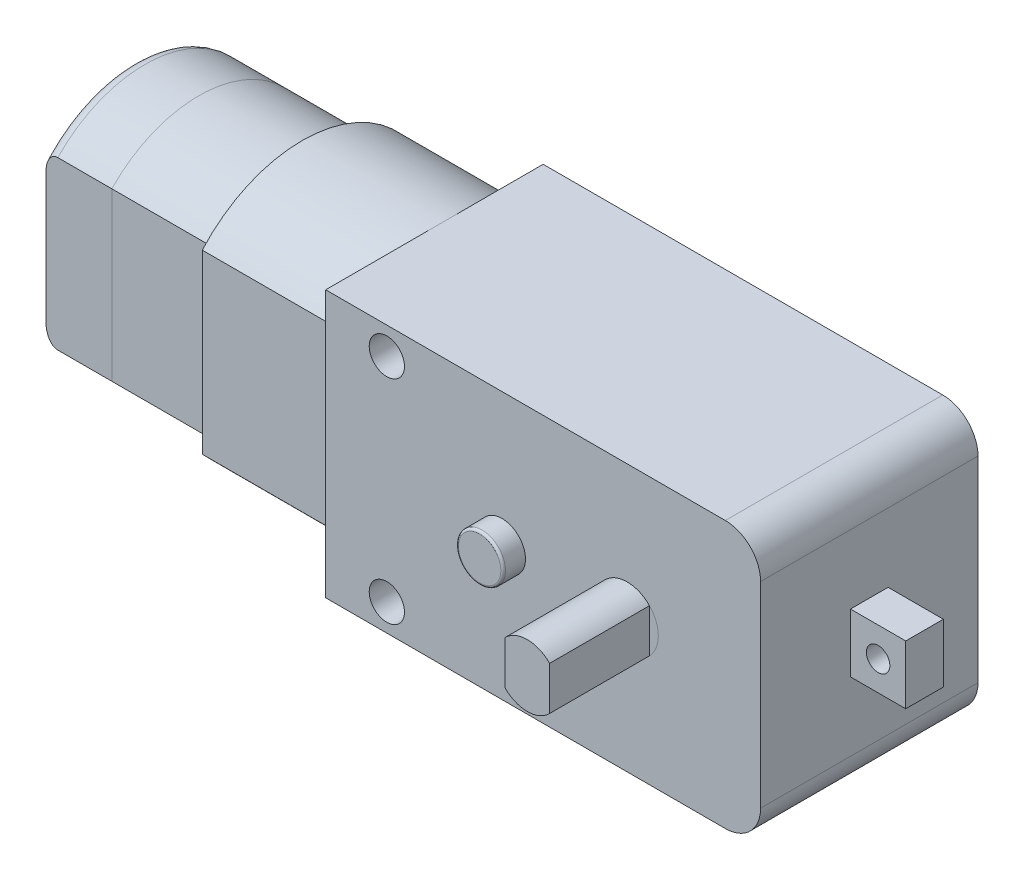
SolidWorks part; units mm, degrees
ref_plane "Alzado" through (0, 0, 0) normal (0, 0, 1) x (1, 0, 0)
ref_plane "Planta" through (0, 0, 0) normal (0, 1, 0) x (1, 0, 0)
ref_plane "Vista lateral" through (0, 0, 0) normal (1, 0, 0) x (0, 0, -1)
sketch "Croquis1" plane through (0, 0, 0) normal (0, 0, 1) x (1, 0, 0)
  line L1 (-18.5, -11.35) -> (15.5, -11.35)
  line L2 (-18.5, -11.35) -> (-18.5, 11.35)
  line L3 (-18.5, 11.35) -> (15.5, 11.35)
  line L4 (18.5, -8.35) -> (18.5, 8.35)
  line L5 (-18.5, -11.35) -> (18.5, 11.35) construction
  line L6 (-18.5, 11.35) -> (18.5, -11.35) construction
  arc A0 (15.5, -11.35) -> (18.5, -8.35) centre (15.5, -8.35) ccw
  arc A1 (15.5, 11.35) -> (18.5, 8.35) centre (15.5, 8.35) cw
  point P0 (0, 0)
  dimension "D3" = 3
  dimension "D1" = 22.7
  dimension "D2" = 37
extrude "Saliente-Extruir1" add sketch "Croquis1" along normal blind 9.25 and the other way blind 9.25
sketch "Croquis2" plane through (-18.5, 0, 0) normal (-1, 0, 0) x (0, 0, 1)
  line L0 (-0.75, -11.35) -> (-0.75, 11.35) construction
  line L1 (7.75, -7.5215) -> (7.75, 7.5215)
  line L2 (-9.25, -7.5215) -> (-9.25, 7.5215)
  line L3 (9.25, 11.35) -> (9.25, -11.35) construction
  line L5 (7.75, -12.1318) -> (7.75, 11.35) construction
  line L6 (-9.25, -12.1318) -> (-9.25, 11.35) construction
  line L7 (-0.75, -12.1318) -> (-0.75, 11.35) construction
  arc A0 (7.75, 7.5215) -> (-9.25, 7.5215) centre (-0.75, 0) ccw
  arc A1 (-9.25, -7.5215) -> (7.75, -7.5215) centre (-0.75, 0) ccw
  point P8 (-0.75, 0)
  dimension "D1" = 22.7
  dimension "D2" = 8.5
  dimension "D3" = 8.5
  dimension "D4" = 1.5
extrude "Saliente-Extruir2" add sketch "Croquis2" along normal blind 12
sketch "Croquis3" plane through (18.5, 0, 0) normal (1, 0, 0) x (0, 0, -1)
  line L1 (1.6, -2.5) -> (-1.6, -2.5)
  line L2 (1.6, -2.5) -> (1.6, 2.5)
  line L3 (1.6, 2.5) -> (-1.6, 2.5)
  line L4 (-1.6, -2.5) -> (-1.6, 2.5)
  line L5 (1.6, -2.5) -> (-1.6, 2.5) construction
  line L6 (1.6, 2.5) -> (-1.6, -2.5) construction
  point P0 (0, 0)
  dimension "D1" = 5
  dimension "D2" = 3.2
extrude "Saliente-Extruir3" add sketch "Croquis3" along normal blind 4.7
sketch "Croquis4" plane through (0, 0, 0) normal (0, 0, 1) x (1, 0, 0)
  line L0 (0, 0) -> (-18.2045, 0) construction
  line L1 (-18.5, -11.35) -> (15.5, -11.35) construction
  line L2 (15.5, 11.35) -> (-18.5, 11.35) construction
  line L3 (-18.5, 11.35) -> (-18.5, -11.35) construction
  circle A0 centre (-13.3, 9.05) radius 1.5
  circle A1 centre (-13.3, -9.05) radius 1.5
  dimension "D1" = 3
  dimension "D2" = 2.3
  dimension "D3" = 2.3
  dimension "D4" = 5.2
  dimension "D5" = 5.2
extrude "Cortar-Extruir1" cut sketch "Croquis4" against normal blind 17.7 and the other way blind 28
sketch "Croquis5" plane through (0, 0, 9.25) normal (0, 0, 1) x (1, 0, 0)
  line L0 (18.5, -8.35) -> (18.5, 8.35) construction
  circle A0 centre (-3.5, 0) radius 2
  point P6 (18.5, 0)
  dimension "D1" = 4
  dimension "D2" = 22
extrude "Saliente-Extruir4" add sketch "Croquis5" along normal blind 1.9
fillet "Redondeo1" radius 0.2 1 edges at (-1.5, 0, 11.15)
sketch "Croquis6" plane through (0, 0, 9.25) normal (0, 0, 1) x (1, 0, 0)
  line L0 (18.5, -8.35) -> (18.5, 8.35) construction
  circle A0 centre (7.15, 0) radius 2.65
  dimension "D1" = 5.3
  dimension "D2" = 11.35
extrude "Cortar-Extruir2" cut sketch "Croquis6" against normal blind 23.9
sketch "Croquis9" plane through (-30.5, 0, 0) normal (-1, 0, 0) x (0, 0, 1)
  line L2 (6.65, -7.5215) -> (6.65, 7.5215)
  line L3 (6.65, -7.0924) -> (6.65, 7.0924)
  line L5 (-8.15, 7.5215) -> (-8.15, -7.5215)
  line L6 (-8.15, 7.0924) -> (-8.15, -7.0924)
  arc A2 (6.9262, 6.7925) -> (-8.4262, 6.7925) centre (-0.75, 0) ccw
  arc A3 (6.65, 7.0924) -> (-8.15, 7.0924) centre (-0.75, 0) ccw
  arc A5 (-8.4262, -6.7925) -> (6.9262, -6.7925) centre (-0.75, 0) ccw
  arc A6 (-8.15, -7.0924) -> (6.65, -7.0924) centre (-0.75, 0) ccw
  dimension "D1" = 1.1
  dimension "D2" = 1.1
  dimension "D3" = 1.1
  dimension "D4" = 1.1
extrude "Saliente-Extruir5" add sketch "Croquis9" along normal blind 8.8 separate body
sketch "Croquis10" plane through (-39.3, 0, 0) normal (-1, 0, 0) x (0, 0, 1)
  line L0 (-8.15, 7.0924) -> (-8.15, -7.0924)
  line L1 (6.65, 7.0924) -> (6.65, -7.0924)
  line L2 (6.65, -7.0924) -> (6.65, 7.0924) construction
  arc A0 (6.65, 7.0924) -> (-8.15, 7.0924) centre (-0.75, 0) ccw
  arc A1 (6.65, 7.0924) -> (-8.15, 7.0924) centre (-0.75, 0) ccw construction
  arc A2 (-8.15, -7.0924) -> (6.65, -7.0924) centre (-0.75, 0) ccw
extrude "Saliente-Extruir6" add sketch "Croquis10" along normal blind 5.6 separate body
fillet "Redondeo2" radius 1 2 edges at (-44.9, 10.25, -0.75) (-44.9, -10.25, -0.75)
sketch "Croquis11" plane through (-44.9, 0, 0) normal (-1, 0, 0) x (0, 0, 1)
  line L0 (6.65, 5.55) -> (6.65, -7.0924) construction
  line L1 (6.65, -7.0924) -> (6.65, -5.55) construction
  line L2 (2.65, 3.6661) -> (2.65, -3.6661)
  line L3 (2.65, 5.55) -> (2.65, -7.0924) construction
  arc A0 (2.65, 3.6661) -> (2.65, -3.6661) centre (-0.75, 0) ccw
  arc A2 (6.65, 7.0924) -> (-8.15, 7.0924) centre (-0.75, 0) ccw construction
  dimension "D1" = 10
  dimension "D2" = 4
extrude "Saliente-Extruir7" add sketch "Croquis11" along normal blind 2 separate body
sketch "Croquis12" plane through (-46.9, 0, 0) normal (-1, 0, 0) x (0, 0, 1)
  circle A0 centre (-0.75, 0) radius 1
  arc A1 (2.65, 3.6661) -> (2.65, -3.6661) centre (-0.75, 0) ccw construction
  dimension "D1" = 2
extrude "Saliente-Extruir8" add sketch "Croquis12" along normal blind 1 separate body
sketch "Croquis13" plane through (0, 0, -8.15) normal (0, 0, -1) x (-1, 0, 0)
  line L0 (44.9, 5.55) -> (44.9, -5.55) construction
  line L1 (39.3, -4) -> (42.3, -4)
  line L2 (39.3, -4) -> (39.3, 4)
  line L3 (39.3, 4) -> (42.3, 4)
  line L4 (42.3, -4) -> (42.3, 4)
  line L5 (39.3, -4) -> (42.3, 4) construction
  line L6 (39.3, 4) -> (42.3, -4) construction
  line L7 (39.3, 7.0924) -> (39.3, -7.0924) construction
  point P0 (40.8, 0)
  point P9 (44.9, 0)
  dimension "D1" = 3
  dimension "D2" = 8
extrude "Saliente-Extruir9" add sketch "Croquis13" along normal blind 1.2 separate body
sketch "Croquis14" plane through (0, 0, 1.6) normal (0, 0, 1) x (1, 0, 0)
  line L0 (18.5, 2.5) -> (23.2, -2.5) construction
  line L1 (23.2, 2.5) -> (18.5, -2.5) construction
  circle A0 centre (20.85, 0) radius 1
  dimension "D1" = 2
extrude "Cortar-Extruir3" cut sketch "Croquis14" against normal blind 4.2
sketch "Croquis15" plane through (0, 0, 0) normal (0, 0, 1) x (1, 0, 0)
  line L0 (7.15, -5.2054) -> (7.15, 5.2054) construction
  line L1 (9.05, -1.8473) -> (9.05, 1.8473)
  line L2 (5.25, -1.8473) -> (5.25, 1.8473)
  line L3 (9.05, -5.2054) -> (9.05, 5.2054) construction
  line L4 (5.25, -5.2054) -> (5.25, 5.2054) construction
  arc A0 (5.25, -1.8473) -> (9.05, -1.8473) centre (7.15, 0) ccw
  circle A1 centre (7.15, 0) radius 2.65 construction
  arc A2 (9.05, 1.8473) -> (5.25, 1.8473) centre (7.15, 0) ccw
  point P7 (7.15, 0)
  dimension "D1" = 1.9
  dimension "D2" = 1.9
extrude "Saliente-Extruir10" add sketch "Croquis15" along normal blind 17.75 and the other way blind 20.25 separate body
sketch "Croquis16" plane through (0, 0, 0) normal (0, 0, 1) x (1, 0, 0)
  circle A0 centre (7.15, 0) radius 2.65
  circle A1 centre (7.15, 0) radius 2.65 construction
extrude "Saliente-Extruir11" add sketch "Croquis16" along normal up to surface (9.25 mm away) and the other way blind 12.25 separate body up to face at (9.8, 0, 9.25)
sketch "草图1" plane through (0, 11.35, 0) normal (0, 1, 0) x (1, 0, 0)
  line L0 (15.5, 9.25) -> (-18.5, 9.25) construction
  line L1 (2.1558, 9.25) -> (12.0231, 9.25)
  line L2 (2.1558, 9.25) -> (2.1558, 21.9258)
  line L3 (2.1558, 21.9258) -> (12.0231, 21.9258)
  line L4 (12.0231, 9.25) -> (12.0231, 21.9258)
extrude "切除-拉伸1" cut sketch "草图1" against normal blind 32 contours L2 L3 L4 L1
